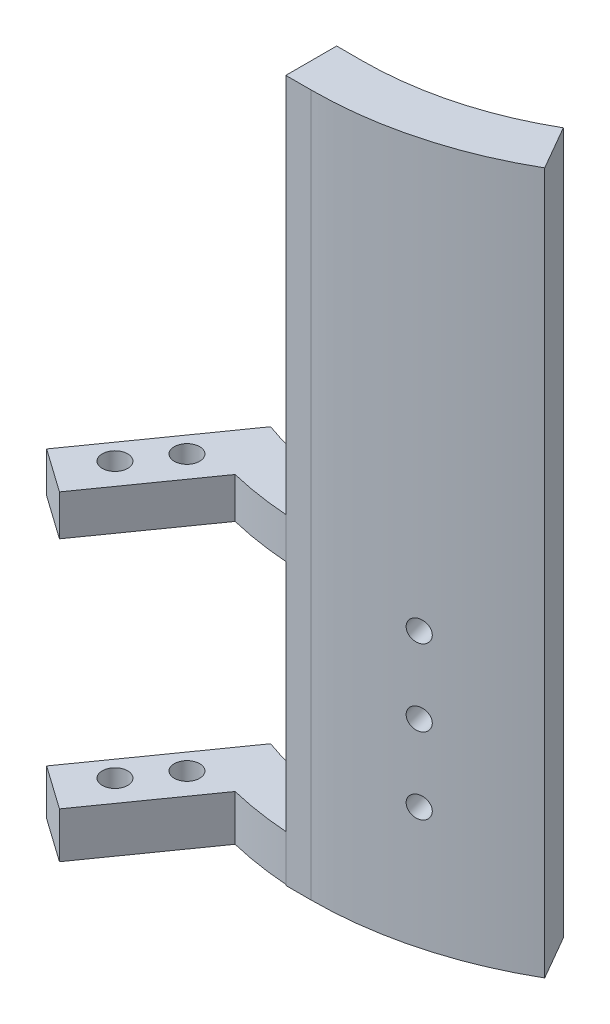
SolidWorks part; units mm, degrees
ref_plane "Front Plane" through (0, 0, 0) normal (0, 0, 1) x (1, 0, 0)
ref_plane "Top Plane" through (0, 0, 0) normal (0, 1, 0) x (1, 0, 0)
ref_plane "Right Plane" through (0, 0, 0) normal (1, 0, 0) x (0, 0, -1)
sketch "Sketch1" plane through (0, 0, 0) normal (0, 0, 1) x (1, 0, 0)
  line L0 (-25, 30) -> (25, 30)
  line L1 (-20, 25) -> (20, 25)
  line L3 (-20, -25) -> (20, -25)
  line L4 (20, 25) -> (20, -25)
  line L5 (-20, 25) -> (20, -25) construction
  line L6 (-20, -25) -> (20, 25) construction
  line L7 (25, 30) -> (25, -30)
  line L8 (-25, -30) -> (25, -30)
  line L9 (-25, 30) -> (-25, 25)
  line L10 (-20, 25) -> (-25, 25)
  line L11 (-20, -25) -> (-25, -25)
  line L12 (-25, -25) -> (-25, -30)
  line L13 (-25, 30) -> (-25, -30) construction
  line L14 (-20, 25) -> (-20, -25) construction
  point P0 (0, 0)
  dimension "D1" = 40
  dimension "D2" = 50
  dimension "D3" = 5
extrude "Boss-Extrude2" add sketch "Sketch1" along normal blind 20
fillet "Fillet1" 2 edges at (-25, 27.5, 20) (-25, 27.5, 0) type full round first side face at (-1.25, 0, 20) second side face at (-1.25, 0, 0) middle face at (-25, 27.5, 10)
fillet "Fillet2" 2 edges at (-25, -27.5, 20) (-25, -27.5, 0) type full round first side face at (1.25, 0, 20) second side face at (1.25, 0, 0) middle face at (-25, -27.5, 10)
sketch "Sketch5" plane through (0, 30, 0) normal (0, 1, 0) x (1, 0, 0)
  circle A0 centre (-15, -10) radius 7 construction
  circle A1 centre (-15, -3) radius 1
  circle A2 centre (-22, -10) radius 1
  circle A3 centre (-15, -17) radius 1
  circle A4 centre (-8, -10) radius 1
  circle A5 centre (-15, -10) radius 5.5
  dimension "D1" = 14
  dimension "D2" = 2
  dimension "D3" = 11
extrude "Cut-Extrude5" cut sketch "Sketch5" against normal through all
sketch "Sketch10" plane through (25, 0, 0) normal (1, 0, 0) x (0, 0, -1)
  line L1 (-15, 28.1801) -> (-15, -28.1801)
  line L3 (-20, -30) -> (-20, 30) construction
  line L4 (-10, 30) -> (-10, 19.211) construction
  line L5 (-20, 30) -> (0, 30) construction
  line L7 (-5, 28.1801) -> (-5, -28.1801)
  line L9 (0, -30) -> (0, 30) construction
  line L10 (0, -30) -> (0, 30)
  line L11 (-20, -30) -> (-20, 30)
  line L12 (-15, 28.1801) -> (-15, 30)
  line L13 (-15, 30) -> (-20, 30)
  line L14 (-15, -28.1801) -> (-15, -30)
  line L15 (-20, -30) -> (0, -30) construction
  line L16 (-15, -30) -> (-20, -30)
  line L17 (-5, -28.1801) -> (-5, -30)
  line L18 (-5, -30) -> (0, -30)
  line L19 (-5, 28.1801) -> (-5, 30)
  line L20 (-5, 30) -> (0, 30)
  dimension "D2" = 5
extrude "Cut-Extrude7" cut sketch "Sketch10" against normal blind 25
fillet "Fillet5" radius 10 4 edges at (0, 27.5, 15) (0, 27.5, 5) (0, -27.5, 15) (0, -27.5, 5)
sketch "Sketch12" plane through (0, -30, 0) normal (0, -1, 0) x (1, 0, 0)
  line L0 (56.2263, -3.3597) -> (61.2225, 5.3027)
  line L1 (25, 15) -> (25, 5)
  arc A0 (56.2263, -3.3597) -> (25, 5) centre (25, -57.5) ccw
  arc A1 (61.2225, 5.3027) -> (25, 15) centre (25, -57.5) ccw
extrude "Boss-Extrude5" add sketch "Sketch12" against normal up to surface (60 mm away) up to face at (-16, 30, 3)
ref_plane "Plane1" through (2.921, 0, 10.9109) normal (-0.2586, 0, -0.966) x (-0.966, 0, 0.2586)
sketch "Sketch13" plane through (2.921, 0, 10.9109) normal (-0.2586, 0, -0.966) x (-0.966, 0, 0.2586)
  line L0 (-39.0195, 30) -> (-39.0195, 0) construction
  line L1 (-22.8565, 30) -> (-55.1825, 30) construction
  line L2 (-39.0195, 0) -> (-39.0195, -30) construction
  line L3 (-55.1825, -30) -> (-22.8565, -30) construction
  circle A0 centre (-39.0195, 15) radius 2.1
  circle A1 centre (-39.0195, 0) radius 2.1
  circle A2 centre (-39.0195, -15) radius 2.1
  dimension "D1" = 4.2
extrude "Cut-Extrude8" cut sketch "Sketch13" against normal blind 60
ref_plane "Plane2" through (4.3924, 0, 18.6716) normal (-0.229, 0, -0.9734) x (-0.9734, 0, 0.229)
ref_plane "Plane3" through (5.1366, 0, 21.8352) normal (-0.229, 0, -0.9734) x (-0.9734, 0, 0.229)
sketch "Sketch15" plane through (0, 30, 0) normal (0, 1, 0) x (1, 0, 0)
  line L0 (8.6603, -5) -> (8.6603, -15)
  arc A0 (8.6603, -5) -> (8.6603, -15) centre (-15, -10) ccw
extrude "Cut-Extrude9" cut sketch "Sketch15" against normal blind 60
sketch "Sketch16" plane through (0, 30, 0) normal (0, 1, 0) x (1, 0, 0)
  line L0 (-6.3079, -33.2204) -> (8.6603, -15)
  line L2 (8.6603, -5) -> (3.4964, -1.3504)
  line L3 (3.4964, -1.3504) -> (-14.7906, -27.2253)
  line L4 (-53.6728, 0.2545) -> (-8.7578, -31.4889) construction
  line L5 (-14.7906, -27.2253) -> (-6.3079, -33.2204)
  line L7 (8.6603, -5) -> (20.0003, -5)
  line L9 (8.6603, -15) -> (20.0003, -15)
  line L10 (20.0003, -5) -> (20.0003, -15)
  line L11 (8.6603, -5) -> (20.0003, -15) construction
  line L12 (8.6603, -15) -> (20.0003, -5) construction
  point P12 (14.3303, -10)
  dimension "D1" = 11.34
extrude "Cut-Extrude10" cut sketch "Sketch16" against normal blind 60
sketch "Sketch17" plane through (0, 16, 0) normal (0, 1, 0) x (1, 0, 0)
  line L0 (-1.0621, -7.6052) -> (3.3607, -1.3472)
  line L1 (-1.0621, -7.6052) -> (-12.6052, -23.9379)
  line L2 (-12.6052, -23.9379) -> (-14.8826, -27.1603)
  line L3 (-53.6728, 0.2545) -> (-8.7578, -31.4889) construction
  line L4 (-14.8826, -27.1603) -> (-6.3079, -33.2204)
  line L5 (-8.7578, -31.4889) -> (-6.3079, -33.2204) construction
  line L6 (-6.3079, -33.2204) -> (7.9981, -12.9783)
  line L7 (-6.3079, -33.2204) -> (11.0067, -8.7213) construction
  line L8 (20.0003, -15) -> (20.0003, -5) construction
  line L9 (20.0003, -15) -> (20.0003, -5)
  arc A0 (3.3607, -1.3472) -> (20.0003, -5) centre (25, 57.5) ccw
  arc A1 (7.9981, -12.9783) -> (20.0003, -14.8274) centre (25, 57.5) ccw
  circle A2 centre (-0.2268, -14.2202) radius 2.5
  circle A3 centre (-6.0907, -22.5172) radius 2.5
  circle M1 centre (-6.0907, -22.5172) radius 2.5
  line M5 (-1.0621, -7.6052) -> (-12.6052, -23.9379)
  circle M8 centre (-0.2268, -14.2202) radius 2.5
  line M10 (-8.7578, -31.4889) -> (-6.3079, -33.2204)
  line M11 (-6.3079, -33.2204) -> (11.0067, -8.7213)
  line M12 (11.0067, -8.7213) -> (-38.8081, 26.485)
extrude "Boss-Extrude6" add sketch "Sketch17" along normal blind 8 contours L2 L4 L0 M10 M11 M12 M5 M1 M8 | A1 L9 A0 L0 M11 M12 region at (-1.7641, 16, 17.8798) region at (13.4225, 16, 8.4463)
sketch "Sketch18" plane through (0, -39, 0) normal (0, 1, 0) x (1, 0, 0)
  line L4 (3.3607, -1.3472) -> (-14.8826, -27.1603)
  line L5 (-14.8826, -27.1603) -> (-6.3079, -33.2204)
  line L6 (-6.3079, -33.2204) -> (7.9981, -12.9783)
  line L7 (20.0003, -14.8274) -> (20.0003, -5)
  line L8 (3.3607, -1.3472) -> (-14.8826, -27.1603)
  line L9 (-14.8826, -27.1603) -> (-6.3079, -33.2204)
  line L10 (-6.3079, -33.2204) -> (7.9981, -12.9783)
  line L12 (25, -5) -> (20.0003, -5)
  line L13 (20.0003, -5) -> (20.0003, -15)
  line L14 (20.0003, -15) -> (25, -15)
  line L15 (61.2225, -5.3027) -> (56.2263, 3.3597)
  line L16 (25, -5) -> (20.0003, -5)
  line L17 (20.0003, -14.8274) -> (20.0003, -15)
  line L18 (20.0003, -15) -> (25, -15)
  line L19 (61.2225, -5.3027) -> (56.2263, 3.3597)
  circle A0 centre (-6.0907, -22.5172) radius 2.5 construction
  circle A1 centre (-0.2268, -14.2202) radius 2.5 construction
  arc A2 (7.9981, -12.9783) -> (20.0003, -14.8274) centre (25, 57.5) ccw
  arc A3 (3.3607, -1.3472) -> (20.0003, -5) centre (25, 57.5) ccw
  arc A4 (7.9981, -12.9783) -> (20.0003, -14.8274) centre (25, 57.5) ccw
  arc A5 (3.3607, -1.3472) -> (20.0003, -5) centre (25, 57.5) ccw
  circle A6 centre (-6.0907, -22.5172) radius 2.5
  circle A7 centre (-0.2268, -14.2202) radius 2.5
  arc A10 (25, -15) -> (61.2225, -5.3027) centre (25, 57.5) ccw
  arc A11 (25, -5) -> (56.2263, 3.3597) centre (25, 57.5) ccw
  arc A12 (25, -15) -> (61.2225, -5.3027) centre (25, 57.5) ccw
  arc A13 (25, -5) -> (56.2263, 3.3597) centre (25, 57.5) ccw
  dimension "D1" = 0
  dimension "D2" = 0
extrude "Boss-Extrude7" add sketch "Sketch18" along normal up to surface (9 mm away) up to face at (34.7728, -30, 7.7299)
sketch "Sketch19" plane through (0, 30, 0) normal (0, 1, 0) x (1, 0, 0)
  line L0 (56.2263, 3.3597) -> (61.2225, -5.3027)
  line L1 (61.2225, -5.3027) -> (56.2263, 3.3597) construction
  line L2 (20.0003, -5) -> (25, -5) construction
  line L3 (25, -5) -> (20.0003, -5)
  line L4 (20.0003, -15) -> (20.0003, -5) construction
  line L5 (20.0003, -5) -> (20.0003, -15)
  line L6 (20.0003, -15) -> (25, -15)
  arc A0 (25, -5) -> (56.2263, 3.3597) centre (25, 57.5) ccw construction
  arc A1 (56.2263, 3.3597) -> (25, -5) centre (25, 57.5) cw
  arc A2 (61.2225, -5.3027) -> (25, -15) centre (25, 57.5) cw
  arc A3 (25, -15) -> (61.2225, -5.3027) centre (25, 57.5) ccw construction
extrude "Boss-Extrude8" add sketch "Sketch19" along normal blind 69
equation "\"éà\"=10"
